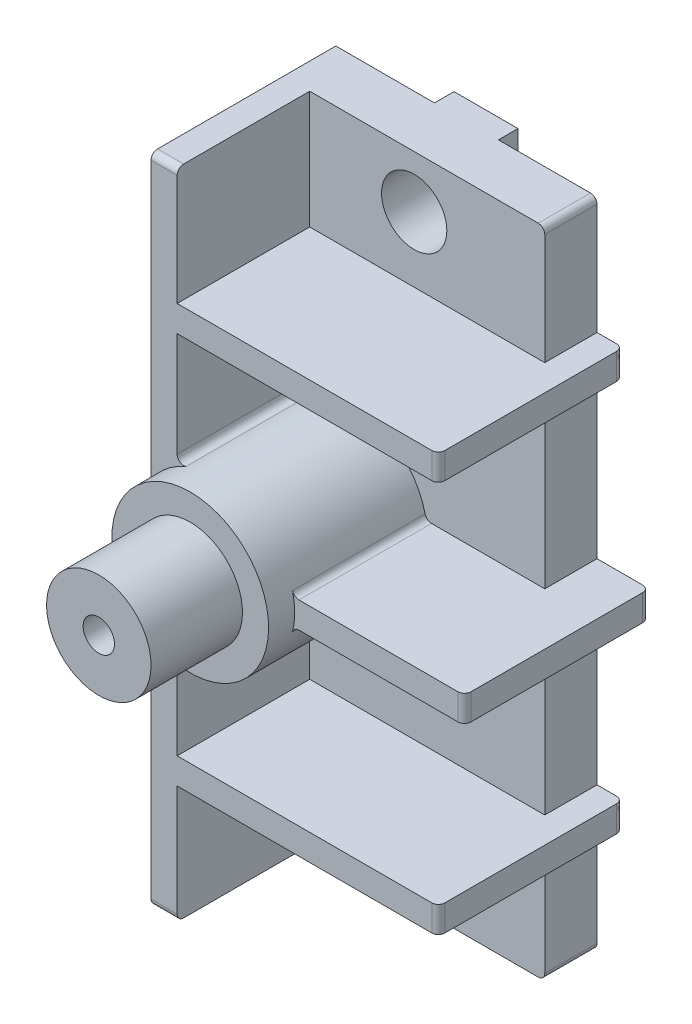
SolidWorks part; units mm, degrees
material "ABS"
ref_plane "Plan de face" through (0, 0, 0) normal (0, 0, 1) x (1, 0, 0)
ref_plane "Plan de dessus" through (0, 0, 0) normal (0, 1, 0) x (1, 0, 0)
ref_plane "Plan de droite" through (0, 0, 0) normal (1, 0, 0) x (0, 0, -1)
sketch "Esquisse1" plane through (0, 0, 0) normal (0, 1, 0) x (1, 0, 0)
  line L0 (7.45, 0) -> (15, 0)
  line L1 (-5, -4) -> (15, -4)
  line L2 (-5, -4) -> (-5, 0)
  line L3 (-5, 0) -> (2.55, 0)
  line L4 (15, -4) -> (15, 0)
  line L5 (2.55, 0) -> (7.45, 0) construction
  line L6 (2.55, 0) -> (2.55, 1.5)
  line L7 (2.55, 1.5) -> (7.45, 1.5)
  line L8 (7.45, 0) -> (7.45, 1.5)
  dimension "D1" = 4.9
  dimension "D2" = 1.5
  dimension "D3" = 20
  dimension "D4" = 4
  dimension "D5" = 5
extrude "Boss.-Extru.1" add sketch "Esquisse1" along normal mid plane 50
sketch "Esquisse3" plane through (0, 0, 0) normal (1, 0, 0) x (0, 0, -1)
  line L0 (0, 6) -> (-16.15, 6)
  line L1 (0, 25) -> (0, -25) construction
  line L2 (-16.15, 6) -> (-16.15, 4)
  line L3 (-16.15, 4) -> (-23.15, 4)
  line L4 (-23.15, 4) -> (-23.15, 1.2)
  line L5 (-23.15, 1.2) -> (0, 1.2)
  line L8 (0, 25) -> (0, -25) construction
  line L9 (0, 1.2) -> (0, 6)
  line L10 (0, 0) -> (-23.15, 0) construction
  dimension "D1" = 2.4
  dimension "D2" = 8
  dimension "D3" = 12
  dimension "D4" = 16.15
  dimension "D5" = 7
revolve "Révolution1" add sketch "Esquisse3" angle 360 about L10
sketch "Esquisse5" plane through (-5, 0, 0) normal (-1, 0, 0) x (0, 0, 1)
  line L0 (0, -25) -> (4, -25) construction
  line L1 (4, 25) -> (14.15, 25)
  line L2 (4, 25) -> (4, -25)
  line L3 (4, -25) -> (14.15, -25)
  line L4 (14.15, 25) -> (14.15, -25)
  line L5 (16.15, -6) -> (16.15, 6) construction
  dimension "D1" = 2
extrude "Boss.-Extru.2" add sketch "Esquisse5" against normal blind 2
sketch "Esquisse6" plane through (0, 0, 14.15) normal (0, 0, 1) x (1, 0, 0)
  line L0 (-5, 3.3166) -> (-5, 25) construction
  line L1 (-5, 16) -> (17, 16)
  line L2 (-5, 16) -> (-5, 14)
  line L3 (-5, 14) -> (17, 14)
  line L4 (17, 16) -> (17, 14)
  line L6 (0, 0) -> (19, 0) construction
  line L7 (17, -16) -> (17, -14)
  line L8 (-5, -14) -> (17, -14)
  line L9 (-5, -16) -> (-5, -14)
  line L10 (-5, -16) -> (17, -16)
  line L13 (5.9161, 1) -> (19, 1)
  line L14 (5.9161, 1) -> (5.9161, -1)
  line L15 (5.9161, -1) -> (19, -1)
  line L16 (19, 1) -> (19, -1)
  circle A0 centre (0, 0) radius 6 construction
  dimension "D1" = 2
  dimension "D2" = 17
  dimension "D3" = 32
  dimension "D4" = 19
extrude "Boss.-Extru.3" add sketch "Esquisse6" against normal up to surface (14.15 mm away) up to face at (11.225, 0, 0)
sketch "Esquisse7" plane through (0, 0, 4) normal (0, 0, 1) x (1, 0, 0)
  line L0 (0, 0) -> (11.6958, 0) construction
  line L1 (15, 25) -> (15, 16) construction
  line L2 (-3, 25) -> (15, 25) construction
  circle A0 centre (5, 21) radius 2.5
  circle A1 centre (5, -21) radius 2.5
  dimension "D1" = 10
  dimension "D2" = 5
  dimension "D3" = 4
extrude "Enlèv. mat.-Extru.1" cut sketch "Esquisse7" against normal through all
fillet "Congé1" radius 0.5 22 edges at (-3, 5.1962, 9.075) (5.9161, 1, 9.075) (5.9161, -1, 9.075) (-3, -5.1962, 9.075) (15, -25, 2) (-4, -25, 14.15) (17, -15, 14.15) (17, -15, 0) (19, 0, 0) (19, 0, 14.15) (15, 25, 2) (17, 15, 0) (17, 15, 14.15) (-4, 25, 14.15) (7.45, -21.4975, -0.75) (7.45, -20.5025, -0.75) (2.55, -21.4975, -0.75) (2.55, -20.5025, -0.75) (2.55, 20.5025, -0.75) (2.55, 21.4975, -0.75) (7.45, 20.5025, -0.75) (7.45, 21.4975, -0.75)
